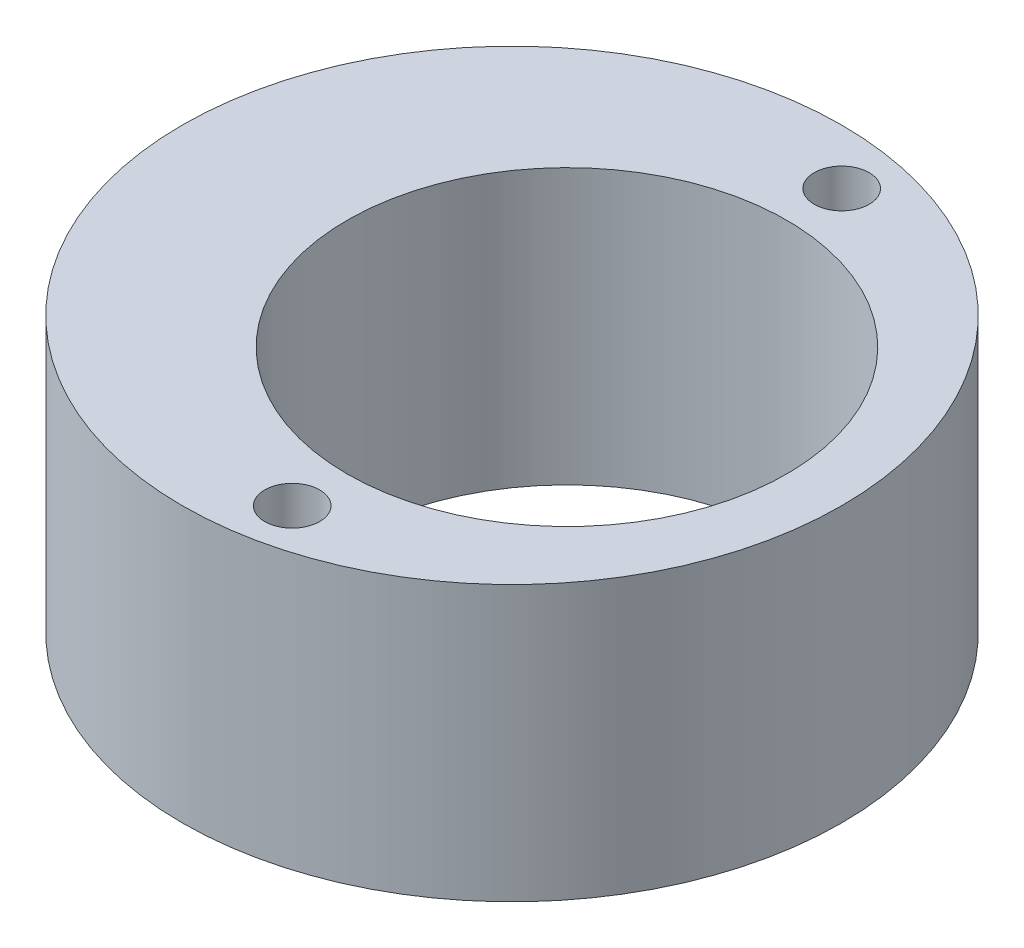
SolidWorks part; units mm, degrees
ref_plane "Front Plane" through (0, 0, 0) normal (0, 0, 1) x (1, 0, 0)
ref_plane "Top Plane" through (0, 0, 0) normal (0, 1, 0) x (1, 0, 0)
ref_plane "Right Plane" through (0, 0, 0) normal (1, 0, 0) x (0, 0, -1)
sketch "Sketch1" plane through (0, 0, 0) normal (0, 1, 0) x (1, 0, 0)
  line L0 (0, 0) -> (-1, 0) construction
  line L1 (0, 8.6459) -> (0, -10.0098) construction
  circle A0 centre (0, 0) radius 4
  circle A1 centre (-1, 0) radius 6
  circle A4 centre (0, 5) radius 0.5
  circle A5 centre (0, -5) radius 0.5
  dimension "D1" = 8
  dimension "D3" = 12
  dimension "D4" = 1
  dimension "D2" = 1
  dimension "D5" = 5
  dimension "D6" = 5
extrude "Boss-Extrude1" add sketch "Sketch1" along normal blind 5
